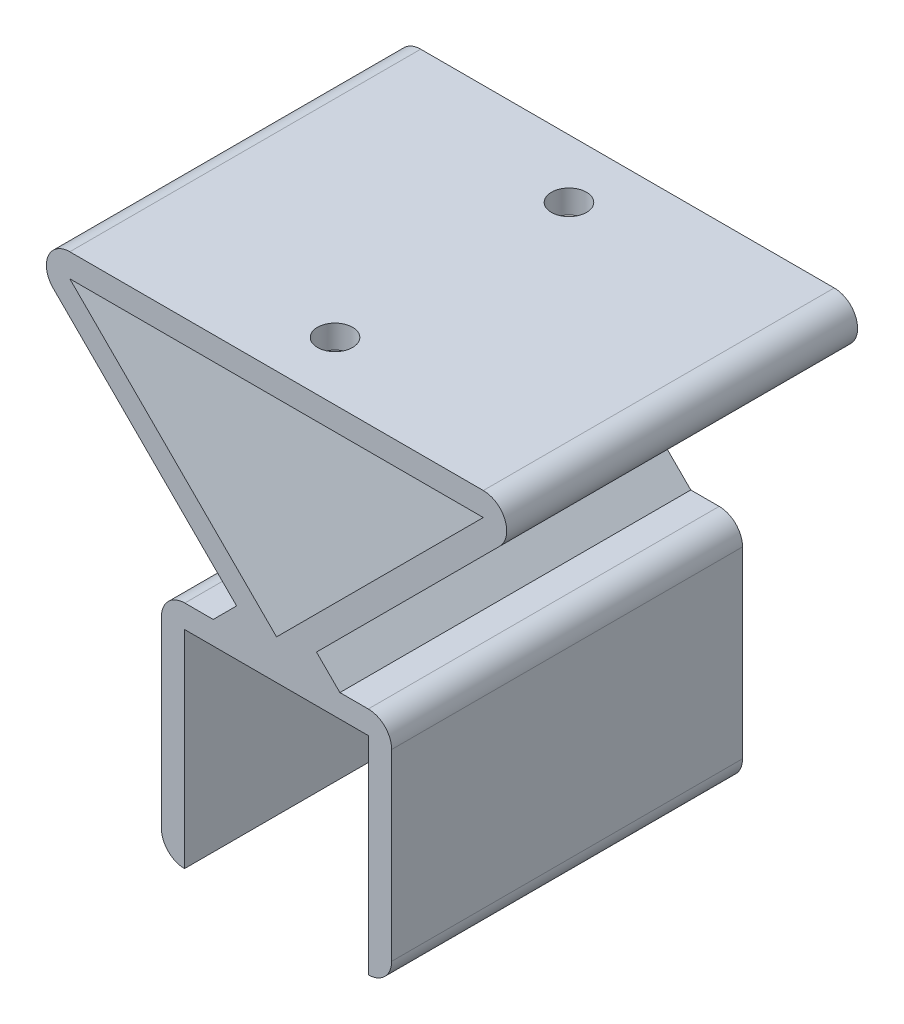
SolidWorks part; units mm, degrees
ref_plane "Front Plane" through (0, 0, 0) normal (0, 0, 1) x (1, 0, 0)
ref_plane "Top Plane" through (0, 0, 0) normal (0, 1, 0) x (1, 0, 0)
ref_plane "Right Plane" through (0, 0, 0) normal (1, 0, 0) x (0, 0, -1)
sketch "Sketch1" plane through (0, 0, 0) normal (0, 0, 1) x (1, 0, 0)
  line L0 (0, 0) -> (22.4506, 22.4506)
  line L1 (22.4506, 22.4506) -> (-22.4506, 22.4506)
  line L2 (-22.4506, 22.4506) -> (0, 0)
  line L3 (0, -3.5921) -> (28.5827, 24.9906)
  line L4 (28.5827, 24.9906) -> (-28.5827, 24.9906)
  line L5 (-28.5827, 24.9906) -> (0, -3.5921)
  dimension "D1" = 31.75
  dimension "D2" = 2.54
extrude "Boss-Extrude1" add sketch "Sketch1" along normal blind 38.1
chamfer "Chamfer1" distance 2.54 angle 45 1 edges at (0, -3.5921, 19.05)
sketch "Sketch2" plane through (0, 0, 38.1) normal (0, 0, 1) x (1, 0, 0)
  line L0 (-1.7961, -1.7961) -> (1.7961, -1.7961) construction
  line L1 (0, -1.7961) -> (12.5, -1.7961)
  line L2 (0, -4.2961) -> (10, -4.2961)
  line L3 (10, -26.7961) -> (12.5, -26.7961)
  line L4 (12.5, -1.7961) -> (12.5, -26.7961)
  line L5 (10, -4.2961) -> (10, -24.2961)
  line L6 (0, -1.7961) -> (-12.5, -1.7961)
  line L8 (-10, -26.7961) -> (-12.5, -26.7961)
  line L9 (-12.5, -1.7961) -> (-12.5, -26.7961)
  line L11 (-10, -4.2961) -> (-10, -24.2961)
  line L12 (0, -4.2961) -> (-10, -4.2961)
  line L13 (10, -24.2961) -> (10, -26.7961)
  line L14 (-10, -24.2961) -> (-10, -26.7961)
  line L15 (0, -26.7961) -> (12.5, -26.7961) construction
  line L16 (0, -24.2961) -> (10, -24.2961) construction
  line L17 (0, -26.7961) -> (-12.5, -26.7961) construction
  line L18 (0, -24.2961) -> (-10, -24.2961) construction
  dimension "D1" = 25
  dimension "D3" = 2.5
extrude "Boss-Extrude2" add sketch "Sketch2" against normal blind 38.1
chamfer "Chamfer2" distance 5.08 angle 45 2 edges
fillet "Fillet1" radius 2.54 6 edges at (-12.5, -26.7961, 19.05) (12.5, -1.7961, 19.05) (-12.5, -1.7961, 19.05) (-28.5827, 24.9906, 19.05) (28.5827, 24.9906, 19.05) (12.5, -26.7961, 19.05)
sketch "Sketch3" plane through (0, 24.9906, 0) normal (0, 1, 0) x (1, 0, 0)
  line L0 (0, -38.1) -> (0, 0) construction
  line L1 (22.4506, -38.1) -> (-22.4506, -38.1) construction
  line L2 (22.4506, 0) -> (-22.4506, 0) construction
  line L3 (22.4506, -19.05) -> (-22.4506, -19.05) construction
  line L4 (22.4506, -38.1) -> (22.4506, 0) construction
  line L5 (-22.4506, 0) -> (-22.4506, -38.1) construction
  circle A0 centre (0, -31.75) radius 1.905
  circle A1 centre (0, -6.35) radius 1.905
  dimension "D1" = 3.81
  dimension "D2" = 25.4
extrude "Cut-Extrude1" cut sketch "Sketch3" against normal up to next
